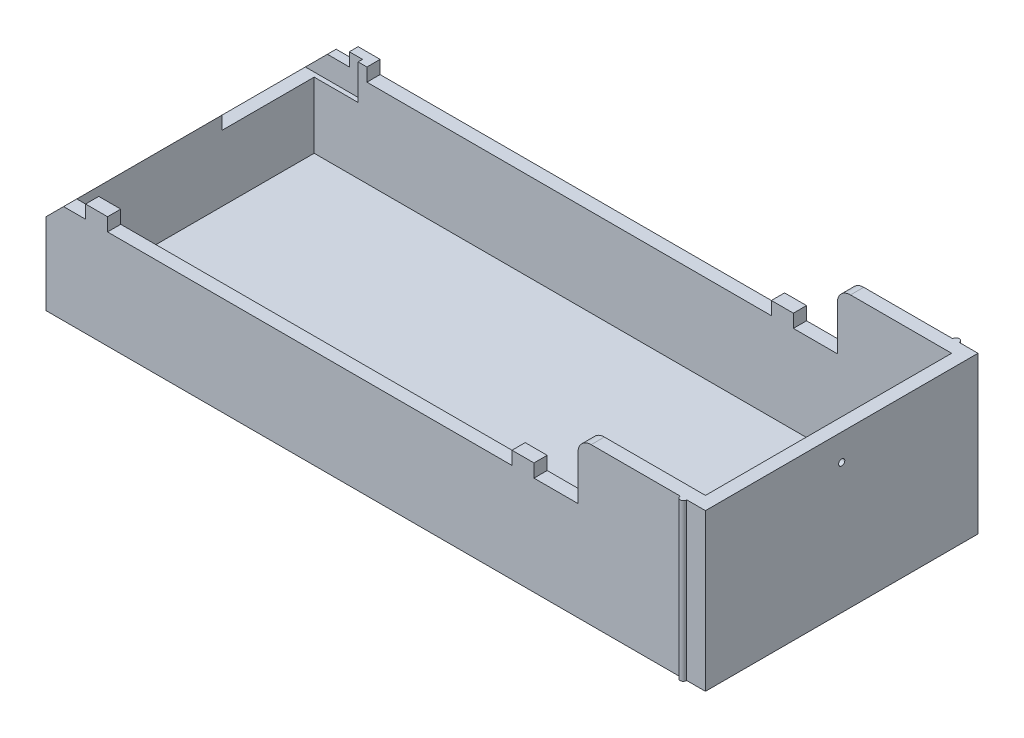
SolidWorks part; units mm, degrees
ref_plane "Plano frontal" through (0, 0, 0) normal (0, 0, 1) x (1, 0, 0)
ref_plane "Plano superior" through (0, 0, 0) normal (0, 1, 0) x (1, 0, 0)
ref_plane "Plano direito" through (0, 0, 0) normal (1, 0, 0) x (0, 0, -1)
sketch "Esboço1" plane through (0, 0, 0) normal (0, 1, 0) x (1, 0, 0)
  line L1 (0, 0) -> (151, 0)
  line L2 (0, 0) -> (0, 62)
  line L3 (0, 62) -> (151, 62)
  line L4 (151, 0) -> (151, 62)
  dimension "D1" = 62
  dimension "D2" = 151
extrude "Ressalto-extrusão1" add sketch "Esboço1" along normal blind 35.6
sketch "Esboço2" plane through (0, 35.6, 0) normal (0, 1, 0) x (1, 0, 0)
  line L0 (151, 62) -> (0, 62) construction
  line L1 (3, 3) -> (148, 3)
  line L2 (3, 3) -> (3, 59)
  line L3 (3, 59) -> (148, 59)
  line L4 (148, 3) -> (148, 59)
  line L5 (0, 62) -> (0, 0) construction
  line L6 (0, 0) -> (151, 0) construction
  line L7 (151, 0) -> (151, 62) construction
  dimension "D1" = 3
  dimension "D2" = 3
  dimension "D3" = 3
  dimension "D4" = 3
extrude "Corte-extrusão1" cut sketch "Esboço2" against normal offset from surface (33.1 mm away) 2.5 up to face at (75.5, 0, -31)
sketch "Esboço3" plane through (0, 35.6, 0) normal (0, 1, 0) x (1, 0, 0)
  line L0 (151, 62) -> (0, 62) construction
  line L1 (0, 0) -> (122, 0)
  line L2 (0, 0) -> (0, 62)
  line L3 (0, 62) -> (122, 62)
  line L4 (122, 0) -> (122, 62)
  line L5 (151, 0) -> (151, 62) construction
  dimension "D1" = 62
  dimension "D2" = 29
extrude "Corte-extrusão2" cut sketch "Esboço3" against normal offset from surface (13.1 mm away) 20 up to face at (75.5, 2.5, -31)
chamfer "Chanfro1" distance 5 1 edges at (0, 22.5, -31)
sketch "Esboço6" plane through (0, 35.6, 0) normal (0, 1, 0) x (1, 0, 0)
  line L0 (151, 62) -> (122, 62) construction
  line L1 (122, 0) -> (151, 0) construction
  line L2 (151, 0) -> (151, 62) construction
  circle A0 centre (146, 62) radius 0.75
  circle A1 centre (146, 0) radius 0.75
  dimension "D1" = 5
  dimension "D2" = 5
  dimension "D3" = 1.5
  dimension "D4" = 1.5
sketch "Esboço7" plane through (151, 0, 0) normal (1, 0, 0) x (0, 0, -1)
  line L0 (0, 35.6) -> (0, 0) construction
  line L1 (0, 35.6) -> (62, 35.6) construction
  circle A0 centre (31, 29.6) radius 0.7
  dimension "D1" = 31
  dimension "D3" = 1.4
  dimension "D2" = 6
extrude "Corte-extrusão6" cut sketch "Esboço7" against normal up to surface (3 mm away) up to face at (148, 19.05, -31)
extrude "Ressalto-extrusão2" add sketch "Esboço6" against normal up to surface (35.6 mm away) up to face at (75.5, 0, -31)
fillet "Filete1" radius 3 2 edges at (122, 35.6, -1.5) (122, 35.6, -60.5)
chamfer "Chanfro2" distance 1 angle 45 3 edges at (0, 8.75, 0) (0, 0, -31) (0, 8.75, -62)
sketch "Esboço8" plane through (0, 22.5, 0) normal (0, 1, 0) x (1, 0, 0)
  line L0 (122, 59) -> (5, 59) construction
  line L1 (15, 59) -> (10, 59)
  line L2 (15, 59) -> (15, 62)
  line L3 (15, 62) -> (10, 62)
  line L4 (10, 59) -> (10, 62)
  line L5 (122, 62) -> (5, 62) construction
  line L6 (5, 0) -> (122, 0) construction
  line L7 (15, 0) -> (10, 0)
  line L8 (15, 0) -> (15, 3)
  line L9 (15, 3) -> (10, 3)
  line L10 (10, 0) -> (10, 3)
  line L11 (5, 3) -> (122, 3) construction
  line L12 (0, 1) -> (0, 61) construction
  line L13 (112, 59) -> (107, 59)
  line L14 (112, 59) -> (112, 62)
  line L15 (112, 62) -> (107, 62)
  line L16 (107, 59) -> (107, 62)
  line L17 (112, 0) -> (107, 0)
  line L18 (112, 0) -> (112, 3)
  line L19 (112, 3) -> (107, 3)
  line L20 (107, 0) -> (107, 3)
  line L21 (122, 59) -> (122, 62) construction
  line L22 (122, 0) -> (122, 3) construction
  point P28 (122, 60.5)
  dimension "D1" = 5
  dimension "D2" = 10
  dimension "D3" = 10
  dimension "D4" = 5
  dimension "D5" = 5
  dimension "D6" = 10
  dimension "D7" = 10
  dimension "D8" = 5
extrude "Ressalto-extrusão3" add sketch "Esboço8" along normal blind 3
sketch "Esboço9" plane through (0, 22.5, 0) normal (0, 1, 0) x (1, 0, 0)
  line L0 (107, 62) -> (15, 62) construction
  line L1 (13, 38) -> (0, 38)
  line L2 (13, 38) -> (13, 60)
  line L3 (13, 60) -> (0, 60)
  line L4 (0, 38) -> (0, 60)
  line L5 (0, 1) -> (0, 61) construction
  dimension "D1" = 13
  dimension "D2" = 22
  dimension "D3" = 2
  dimension "D4" = 13
extrude "Corte-extrusão7" cut sketch "Esboço9" against normal up to vertex (5 mm away) and the other way blind 3 up to point (0, 17.5, -1)
